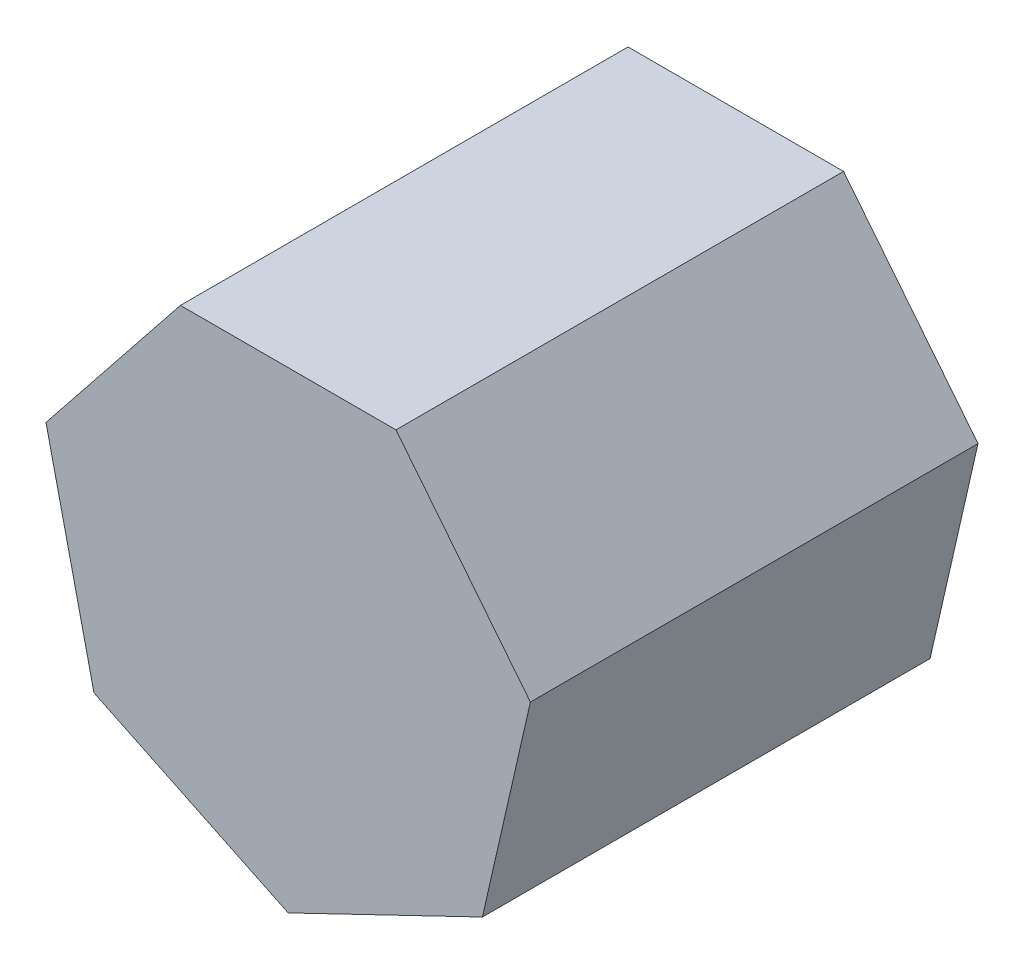
SolidWorks part; units mm, degrees
ref_plane "Front Plane" through (0, 0, 0) normal (0, 0, 1) x (1, 0, 0)
ref_plane "Top Plane" through (0, 0, 0) normal (0, 1, 0) x (1, 0, 0)
ref_plane "Right Plane" through (0, 0, 0) normal (1, 0, 0) x (0, 0, -1)
sketch "Sketch1" plane through (0, 0, 0) normal (0, 0, 1) x (1, 0, 0)
  line L1 (0, -110.9916) -> (86.7767, -69.2021)
  line L2 (86.7767, -69.2021) -> (108.2088, 24.698)
  line L3 (108.2088, 24.698) -> (48.1575, 100)
  line L4 (48.1575, 100) -> (-48.1575, 100)
  line L5 (-48.1575, 100) -> (-108.2088, 24.698)
  line L6 (-108.2088, 24.698) -> (-86.7767, -69.2021)
  line L7 (-86.7767, -69.2021) -> (0, -110.9916)
  circle A0 centre (0, 0) radius 100 construction
  point P1 (0, 0)
  dimension "D1" = 200
extrude "Boss-Extrude1" add sketch "Sketch1" along normal blind 200
